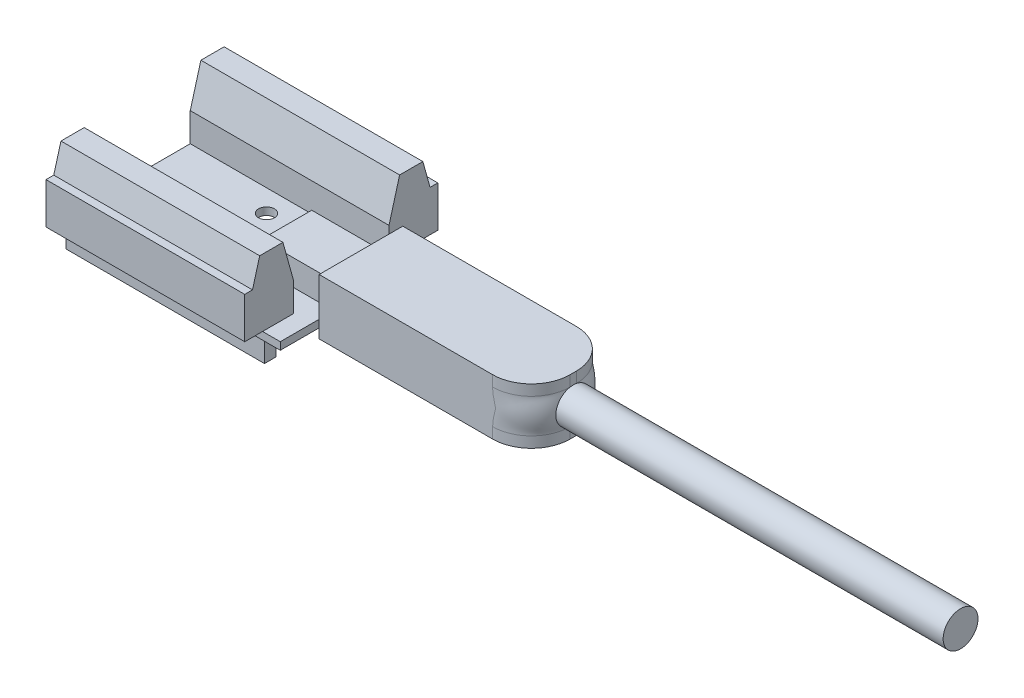
SolidWorks part; units mm, degrees
ref_plane "Front" through (0, 0, 0) normal (0, 0, 1) x (1, 0, 0)
ref_plane "Top" through (0, 0, 0) normal (0, 1, 0) x (1, 0, 0)
ref_plane "Right" through (0, 0, 0) normal (1, 0, 0) x (0, 0, -1)
sketch "Sketch2" plane through (0, 0, 0) normal (0, 1, 0) x (1, 0, 0)
  line L1 (13.97, 10.16) -> (-13.97, 10.16)
  line L2 (13.97, 10.16) -> (13.97, -10.16)
  line L3 (13.97, -10.16) -> (-13.97, -10.16)
  line L4 (-13.97, 10.16) -> (-13.97, -10.16)
  line L5 (0, -10.16) -> (0, 10.16) construction
  line L6 (13.97, 0) -> (-13.97, 0) construction
  point P0 (0, 0)
  dimension "D1" = 20.32
  dimension "D2" = 27.94
extrude "Boss-Extrude1" add sketch "Sketch2" along normal blind 0.9652
sketch "Sketch3" plane through (0, 0.9652, 0) normal (0, 1, 0) x (1, 0, 0)
  line L0 (-1.27, 3.302) -> (-1.27, -3.302) construction
  line L1 (-1.27, 0) -> (0, 0) construction
  line L2 (-13.97, 10.16) -> (-13.97, -10.16) construction
  circle A0 centre (-1.27, 3.302) radius 1.016
  circle A1 centre (-1.27, -3.302) radius 1.016
  dimension "D2" = 2.032
  dimension "D3" = 11.684
  dimension "D1" = 6.604
extrude "Cut-Extrude1" cut sketch "Sketch3" against normal through all
sketch "Sketch4" plane through (0, 0.9652, 0) normal (0, 1, 0) x (1, 0, 0)
  line L0 (13.97, -10.16) -> (13.97, 10.16) construction
  line L1 (4.624, 3.25) -> (14.224, 3.25)
  line L2 (4.624, 3.25) -> (4.624, -3.25)
  line L3 (4.624, -3.25) -> (14.224, -3.25)
  line L4 (14.224, 3.25) -> (14.224, -3.25)
  line L5 (9.424, -3.25) -> (9.424, 3.25) construction
  line L6 (4.624, 0) -> (14.224, 0) construction
  point P140 (9.424, 0)
  dimension "D1" = 0.254
  dimension "D2" = 9.6
  dimension "D3" = 6.5
extrude "Boss-Extrude2" add sketch "Sketch4" along normal blind 3.32
sketch "Sketch5" plane through (-13.97, 0, 0) normal (-1, 0, 0) x (0, 0, 1)
  line L0 (-6.16, 0.9652) -> (-12.46, 0.9652)
  line L1 (-10.16, 0.9652) -> (10.16, 0.9652) construction
  line L2 (-12.46, 0.9652) -> (-12.46, 6.2652)
  line L3 (-12.46, 6.2652) -> (-11.46, 6.2652)
  line L4 (-11.46, 6.2652) -> (-10.5317, 9.6152)
  line L5 (-10.5317, 9.6152) -> (-7.5317, 9.6152)
  line L6 (-7.5317, 9.6152) -> (-6.16, 4.6652)
  line L7 (-6.16, 4.6652) -> (-6.16, 0.9652)
  line L8 (-9.0317, 9.6152) -> (-9.0317, 0.9652) construction
  line L9 (-10.16, 0.9652) -> (-10.16, 0) construction
  line L10 (0, 0) -> (0, 4.2852) construction
  line L11 (-3.25, 4.2852) -> (3.25, 4.2852) construction
  line L12 (9.0317, 9.6152) -> (9.0317, 0.9652) construction
  line L13 (6.16, 4.6652) -> (6.16, 0.9652)
  line L14 (7.5317, 9.6152) -> (6.16, 4.6652)
  line L15 (10.5317, 9.6152) -> (7.5317, 9.6152)
  line L16 (11.46, 6.2652) -> (10.5317, 9.6152)
  line L17 (12.46, 6.2652) -> (11.46, 6.2652)
  line L18 (12.46, 0.9652) -> (12.46, 6.2652)
  line L19 (6.16, 0.9652) -> (12.46, 0.9652)
  point P16 (-10.16, 0.4826)
  dimension "D1" = 6.3
  dimension "D2" = 5.3
  dimension "D3" = 8.65
  dimension "D4" = 1
  dimension "D5" = 3.7
  dimension "D6" = 2.3
  dimension "D7" = 3
extrude "Boss-Extrude3" add sketch "Sketch5" against normal blind 25.654
sketch "Sketch6" plane through (-13.97, 0, 0) normal (-1, 0, 0) x (0, 0, 1)
  line L0 (-10.16, 0) -> (10.16, 0) construction
  line L1 (-8.41, 0) -> (-9.91, 0)
  line L2 (-8.41, 0) -> (-8.41, -2.75)
  line L3 (-8.41, -2.75) -> (-9.91, -2.75)
  line L4 (-9.91, 0) -> (-9.91, -2.75)
  line L5 (-9.16, -2.75) -> (-9.16, 0) construction
  line L6 (-8.41, -1.375) -> (-9.91, -1.375) construction
  line L7 (-10.16, 0.9652) -> (-10.16, 0) construction
  line L8 (0, 0) -> (0, 4.2852) construction
  line L9 (-3.25, 4.2852) -> (3.25, 4.2852) construction
  line L10 (8.41, -1.375) -> (9.91, -1.375) construction
  line L11 (9.16, -2.75) -> (9.16, 0) construction
  line L12 (9.91, 0) -> (9.91, -2.75)
  line L13 (8.41, -2.75) -> (9.91, -2.75)
  line L14 (8.41, 0) -> (8.41, -2.75)
  line L15 (8.41, 0) -> (9.91, 0)
  point P20 (9.16, -1.375)
  point P136 (-9.16, -1.375)
  dimension "D1" = 1
  dimension "D2" = 1.5
  dimension "D3" = 2.75
extrude "Boss-Extrude4" add sketch "Sketch6" against normal blind 25.654
sketch "Sketch7" plane through (14.224, 0, 0) normal (1, 0, 0) x (0, 0, -1)
  line L0 (-3.25, 4.2852) -> (3.25, 0.9652) construction
  line L1 (-5.4, -0.9748) -> (5.4, -0.9748)
  line L2 (-5.4, -0.9748) -> (-5.4, 6.2252)
  line L3 (-5.4, 6.2252) -> (5.4, 6.2252)
  line L4 (5.4, -0.9748) -> (5.4, 6.2252)
  line L5 (0, 6.2252) -> (0, -0.9748) construction
  line L6 (-5.4, 2.6252) -> (5.4, 2.6252) construction
  point P0 (0, 2.6252)
  point P6 (0, 2.6252)
  dimension "D1" = 7.2
  dimension "D2" = 10.8
extrude "Boss-Extrude5" add sketch "Sketch7" along normal blind 27.4
sketch "Sketch8" plane through (41.624, 0, 0) normal (1, 0, 0) x (0, 0, -1)
  circle A0 centre (0, 2.6252) radius 2.25
  dimension "D1" = 4.5
extrude "Boss-Extrude6" add sketch "Sketch8" along normal blind 50
fillet "Fillet1" radius 5 2 edges at (41.624, 2.6252, -5.4) (41.624, 2.6252, 5.4)
